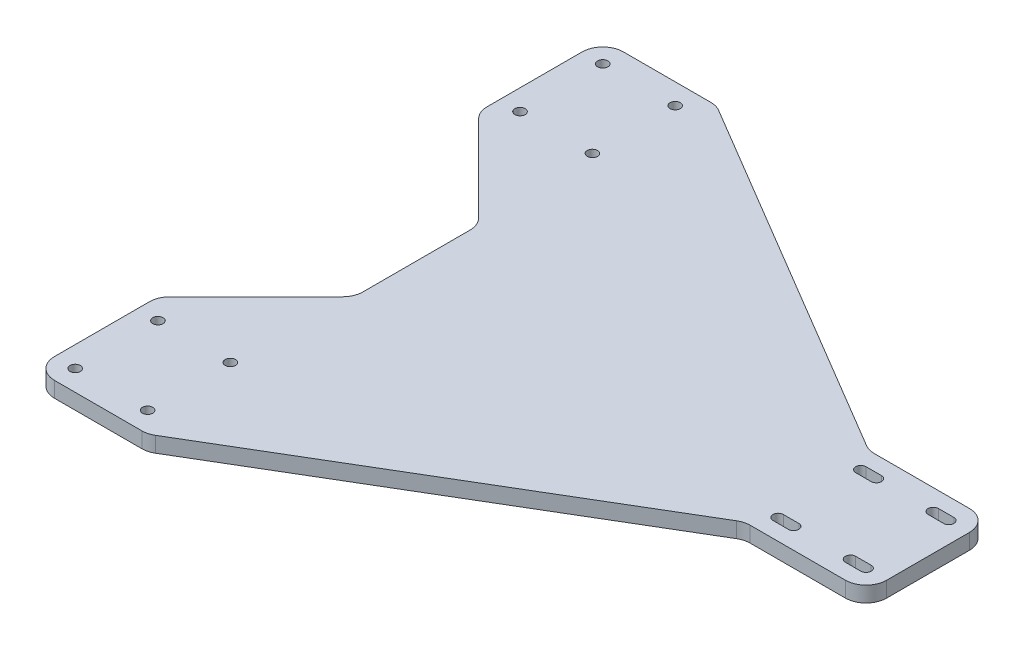
SolidWorks part; units mm, degrees
material "6061-O (SS)"
ref_plane "Plan de face" through (0, 0, 0) normal (0, 0, 1) x (1, 0, 0)
ref_plane "Plan de dessus" through (0, 0, 0) normal (0, 1, 0) x (1, 0, 0)
ref_plane "Plan de droite" through (0, 0, 0) normal (1, 0, 0) x (0, 0, -1)
sketch "Esquisse1" plane through (0, 0, 0) normal (0, 1, 0) x (1, 0, 0)
  line L1 (58.95, -55) -> (-58.95, -55)
  line L2 (58.95, -55) -> (58.95, 55)
  line L3 (58.95, 55) -> (-58.95, 55)
  line L4 (-58.95, -55) -> (-58.95, 55)
  line L5 (58.95, -55) -> (-58.95, 55) construction
  line L6 (58.95, 55) -> (-58.95, -55) construction
  point P0 (0, 0)
  dimension "D1" = 110
  dimension "D2" = 117.9
extrude "Boss.-Extru.1" add sketch "Esquisse1" along normal blind 3
sketch "Esquisse2" plane through (0, 0, 0) normal (0, 1, 0) x (1, 0, 0)
  line L0 (-58.95, -55) -> (58.95, -55) construction
  line L1 (-54.95, -35) -> (-40.95, -35) construction
  line L2 (-54.95, -35) -> (-54.95, -51) construction
  line L3 (-54.95, -51) -> (-40.95, -51) construction
  line L4 (-40.95, -35) -> (-40.95, -51) construction
  line L5 (-54.95, -35) -> (-40.95, -51) construction
  line L6 (-54.95, -51) -> (-40.95, -35) construction
  line L7 (-58.95, 55) -> (-58.95, -55) construction
  line L8 (0, 0) -> (-58.95, 0) construction
  line L9 (-54.95, 51) -> (-40.95, 35) construction
  line L10 (-54.95, 35) -> (-40.95, 51) construction
  line L11 (-40.95, 35) -> (-40.95, 51) construction
  line L12 (-54.95, 51) -> (-40.95, 51) construction
  line L13 (-54.95, 35) -> (-54.95, 51) construction
  line L14 (-54.95, 35) -> (-40.95, 35) construction
  line L15 (46.45, 0) -> (53.45, 8) construction
  line L16 (39.45, 8) -> (53.45, 8) construction
  line L17 (39.45, 8) -> (39.45, -8) construction
  line L18 (39.45, -8) -> (53.45, -8) construction
  line L19 (53.45, 8) -> (53.45, -8) construction
  line L20 (39.45, 8) -> (46.45, 0) construction
  line L21 (39.45, -8) -> (46.45, 0) construction
  line L22 (46.45, 0) -> (53.45, -8) construction
  line L23 (0, 0) -> (58.95, 0) construction
  line L24 (58.95, -55) -> (58.95, 55) construction
  line L25 (58.95, 12) -> (35.45, 12)
  line L26 (35.45, 12) -> (-36.95, 55)
  line L27 (58.95, 55) -> (-58.95, 55) construction
  line L28 (-36.95, 55) -> (58.95, 55)
  line L29 (58.95, 55) -> (58.95, 12)
  line L30 (58.95, -12) -> (35.45, -12)
  line L31 (58.95, -55) -> (58.95, -12)
  line L32 (-36.95, -55) -> (58.95, -55)
  line L33 (35.45, -12) -> (-36.95, -55)
  line L34 (-58.95, -31) -> (-39.95, -12)
  line L35 (-39.95, -12) -> (-39.95, 12)
  line L36 (-39.95, 12) -> (-58.95, 31)
  line L37 (-58.95, 31) -> (-58.95, -31)
  line L38 (37.95, 8) -> (40.95, 8) construction
  line L39 (37.95, 9) -> (40.95, 9)
  line L40 (37.95, 7) -> (40.95, 7)
  line L41 (54.95, 8) -> (51.95, 8) construction
  line L42 (54.95, 7) -> (51.95, 7)
  line L43 (54.95, 9) -> (51.95, 9)
  line L44 (37.95, -8) -> (40.95, -8) construction
  line L45 (37.95, -7) -> (40.95, -7)
  line L46 (37.95, -9) -> (40.95, -9)
  line L47 (54.95, -8) -> (51.95, -8) construction
  line L48 (54.95, -9) -> (51.95, -9)
  line L49 (54.95, -7) -> (51.95, -7)
  circle A0 centre (-40.95, -35) radius 1
  circle A1 centre (-54.95, -35) radius 1
  circle A2 centre (-54.95, -51) radius 1
  circle A3 centre (-40.95, -51) radius 1
  circle A4 centre (-40.95, 51) radius 1
  circle A5 centre (-54.95, 51) radius 1
  circle A6 centre (-54.95, 35) radius 1
  circle A7 centre (-40.95, 35) radius 1
  arc A12 (37.95, 9) -> (37.95, 7) centre (37.95, 8) ccw
  arc A13 (40.95, 7) -> (40.95, 9) centre (40.95, 8) ccw
  arc A14 (54.95, 7) -> (54.95, 9) centre (54.95, 8) ccw
  arc A15 (51.95, 9) -> (51.95, 7) centre (51.95, 8) ccw
  arc A16 (37.95, -7) -> (37.95, -9) centre (37.95, -8) ccw
  arc A17 (40.95, -9) -> (40.95, -7) centre (40.95, -8) ccw
  arc A18 (54.95, -9) -> (54.95, -7) centre (54.95, -8) ccw
  arc A19 (51.95, -7) -> (51.95, -9) centre (51.95, -8) ccw
  point P0 (-47.95, -43)
  point P25 (-47.95, 43)
  point P26 (46.45, 0)
  point P33 (39.45, 8)
  point P52 (-39.95, 0)
  point P58 (53.45, 8)
  point P65 (39.45, -8)
  point P72 (53.45, -8)
  dimension "D3" = 2
  dimension "D4" = 4
  dimension "D5" = 4
  dimension "D6" = 1
  dimension "D1" = 16
  dimension "D2" = 14
  dimension "D7" = 14
  dimension "D8" = 16
  dimension "D9" = 5.5
  dimension "D10" = 4
  dimension "D11" = 4
  dimension "D12" = 4
  dimension "D13" = 4
  dimension "D14" = 4
  dimension "D15" = 4
  dimension "D16" = 1
  dimension "D17" = 1.5
extrude "Enlèv. mat.-Extru.1" cut sketch "Esquisse2" along normal through all
fillet "Congé1" radius 4 12 edges at (35.45, 1.5, 12) (58.95, 1.5, 12) (58.95, 1.5, -12) (35.45, 1.5, -12) (-36.95, 1.5, -55) (-58.95, 1.5, -55) (-58.95, 1.5, -31) (-39.95, 1.5, -12) (-39.95, 1.5, 12) (-58.95, 1.5, 31) (-58.95, 1.5, 55) (-36.95, 1.5, 55)
sketch "Esquisse3" plane through (0, 0, 0) normal (0, 1, 0) x (1, 0, 0)
  line L1 (11, -11) -> (-11, -11) construction
  line L2 (11, -11) -> (11, 11) construction
  line L3 (11, 11) -> (-11, 11) construction
  line L4 (-11, -11) -> (-11, 11) construction
  line L5 (11, -11) -> (-11, 11) construction
  line L6 (11, 11) -> (-11, -11) construction
  line L7 (-11.5, 11) -> (-10.5, 11) construction
  line L8 (-11.5, 13) -> (-10.5, 13)
  line L9 (-11.5, 9) -> (-10.5, 9)
  line L10 (0, 0) -> (-11, 0) construction
  line L11 (0, 0) -> (0, 11) construction
  line L12 (11.5, 11) -> (10.5, 11) construction
  line L13 (11.5, 13) -> (10.5, 13)
  line L14 (11.5, 9) -> (10.5, 9)
  line L15 (11.5, -11) -> (10.5, -11) construction
  line L16 (11.5, -13) -> (10.5, -13)
  line L17 (11.5, -9) -> (10.5, -9)
  line L18 (-11.5, -11) -> (-10.5, -11) construction
  line L19 (-11.5, -13) -> (-10.5, -13)
  line L20 (-11.5, -9) -> (-10.5, -9)
  arc A4 (-11.5, 13) -> (-11.5, 9) centre (-11.5, 11) ccw
  arc A5 (-10.5, 9) -> (-10.5, 13) centre (-10.5, 11) ccw
  arc A6 (11.5, 13) -> (11.5, 9) centre (11.5, 11) cw
  arc A7 (10.5, 9) -> (10.5, 13) centre (10.5, 11) cw
  arc A8 (11.5, -13) -> (11.5, -9) centre (11.5, -11) ccw
  arc A9 (10.5, -9) -> (10.5, -13) centre (10.5, -11) ccw
  arc A10 (-11.5, -13) -> (-11.5, -9) centre (-11.5, -11) cw
  arc A11 (-10.5, -9) -> (-10.5, -13) centre (-10.5, -11) cw
  circle A12 centre (0, 0) radius 8
  point P0 (0, 0)
  point P8 (-11, 11)
  point P22 (11, 11)
  point P29 (11, -11)
  point P36 (-11, -11)
  dimension "D3" = 2
  dimension "D6" = 16
  dimension "D1" = 22
  dimension "D2" = 22
  dimension "D5" = 0.5
extrude "Enlèv. mat.-Extru.2" [suppressed] cut sketch "Esquisse3" along normal through all contours A12
sketch "Esquisse4" plane through (0, 0, 0) normal (0, -1, 0) x (1, 0, 0)
  line L4 (0, 0) -> (6.2905, 0) construction
  line L11 (2.9021, 16.3913) -> (0.8595, 12.9521)
  line L13 (1.261, 11.3761) -> (2.2498, 10.7889)
  line L18 (2.2498, 10.7889) -> (4.8796, 15.2168)
  line L19 (4.8796, 15.2168) -> (2.9021, 16.3913)
  line L21 (3.5647, 13.0028) -> (9.7122, 9.3517) construction
  line L22 (7.939, 13.3671) -> (7.3805, 12.4266) construction
  line L23 (0.2722, 11.9634) -> (2.2498, 10.7889) construction
  line L24 (34.5057, 12.5608) -> (-36.0057, 54.4392) construction
  line L25 (0.2722, 11.9634) -> (0.8595, 12.9521) construction
  line L26 (8.3973, 7.1377) -> (11.0271, 11.5657)
  line L27 (9.386, 6.5505) -> (8.3973, 7.1377)
  line L28 (13.0046, 10.3912) -> (10.962, 6.952)
  line L29 (11.0271, 11.5657) -> (13.0046, 10.3912)
  line L36 (-36.0057, -54.4392) -> (34.5057, -12.5608) construction
  line L37 (-20.806, -41.8884) -> (-19.896, -36.9719)
  line L38 (-19.896, -36.9719) -> (-23.6988, -33.7255)
  line L39 (-23.6988, -33.7255) -> (-28.4116, -35.3956)
  line L40 (-28.4116, -35.3956) -> (-29.3216, -40.3121)
  line L41 (-29.3216, -40.3121) -> (-25.5189, -43.5585)
  line L42 (-25.5189, -43.5585) -> (-20.806, -41.8884)
  line L91 (-39.95, 0) -> (-65.3468, 0) construction
  line L92 (-24.2263, -32.4915) -> (-23.3162, -27.575)
  line L153 (-23.3162, -27.575) -> (-27.119, -24.3286)
  line L154 (-27.119, -24.3286) -> (-31.8318, -25.9987)
  line L155 (-31.8318, -25.9987) -> (-32.7418, -30.9152)
  line L156 (-32.7418, -30.9152) -> (-28.9391, -34.1616)
  line L157 (-28.9391, -34.1616) -> (-24.2263, -32.4915)
  line L158 (-27.6465, -23.0945) -> (-26.7364, -18.178)
  line L159 (-26.7364, -18.178) -> (-30.5392, -14.9317)
  line L160 (-30.5392, -14.9317) -> (-35.252, -16.6018)
  line L161 (-35.252, -16.6018) -> (-36.162, -21.5183)
  line L162 (-36.162, -21.5183) -> (-32.3593, -24.7646)
  line L163 (-32.3593, -24.7646) -> (-27.6465, -23.0945)
  line L164 (-14.3782, -34.2279) -> (-13.4681, -29.3115)
  line L165 (-13.4681, -29.3115) -> (-17.2709, -26.0651)
  line L166 (-17.2709, -26.0651) -> (-21.9837, -27.7352)
  line L167 (-21.9837, -27.7352) -> (-22.8938, -32.6517)
  line L168 (-22.8938, -32.6517) -> (-19.091, -35.898)
  line L169 (-19.091, -35.898) -> (-14.3782, -34.2279)
  line L170 (-17.8041, -24.8152) -> (-16.8941, -19.8987)
  line L171 (-16.8941, -19.8987) -> (-20.6968, -16.6524)
  line L172 (-20.6968, -16.6524) -> (-25.4097, -18.3225)
  line L173 (-25.4097, -18.3225) -> (-26.3197, -23.239)
  line L174 (-26.3197, -23.239) -> (-22.5169, -26.4853)
  line L175 (-22.5169, -26.4853) -> (-17.8041, -24.8152)
  line L176 (-34.0743, -30.755) -> (-33.1643, -25.8385)
  line L177 (-33.1643, -25.8385) -> (-36.967, -22.5921)
  line L178 (-36.967, -22.5921) -> (-41.6799, -24.2622)
  line L179 (-41.6799, -24.2622) -> (-42.5899, -29.1787)
  line L180 (-42.5899, -29.1787) -> (-38.7872, -32.4251)
  line L181 (-38.7872, -32.4251) -> (-34.0743, -30.755)
  line L182 (-11.3762, -17.1548) -> (-10.4662, -12.2383)
  line L183 (-10.4662, -12.2383) -> (-14.269, -8.9919)
  line L184 (-14.269, -8.9919) -> (-18.9818, -10.662)
  line L185 (-18.9818, -10.662) -> (-19.8918, -15.5785)
  line L186 (-19.8918, -15.5785) -> (-16.0891, -18.8249)
  line L187 (-16.0891, -18.8249) -> (-11.3762, -17.1548)
  line L188 (-21.2243, -15.4183) -> (-20.3143, -10.5018)
  line L189 (-20.3143, -10.5018) -> (-24.117, -7.2554)
  line L190 (-24.117, -7.2554) -> (-28.8299, -8.9256)
  line L191 (-28.8299, -8.9256) -> (-29.7399, -13.842)
  line L192 (-29.7399, -13.842) -> (-25.9371, -17.0884)
  line L193 (-25.9371, -17.0884) -> (-21.2243, -15.4183)
  line L194 (-24.6388, -6.0372) -> (-23.7287, -1.1207)
  line L195 (-23.7287, -1.1207) -> (-27.5315, 2.1257)
  line L196 (-27.5315, 2.1257) -> (-32.2443, 0.4556)
  line L197 (-32.2443, 0.4556) -> (-33.1544, -4.4609)
  line L198 (-33.1544, -4.4609) -> (-29.3516, -7.7073)
  line L199 (-29.3516, -7.7073) -> (-24.6388, -6.0372)
  line L200 (-14.7907, -7.7736) -> (-13.8806, -2.8572)
  line L201 (-13.8806, -2.8572) -> (-17.6834, 0.3892)
  line L202 (-17.6834, 0.3892) -> (-22.3962, -1.2809)
  line L203 (-22.3962, -1.2809) -> (-23.3063, -6.1974)
  line L204 (-23.3063, -6.1974) -> (-19.5035, -9.4438)
  line L205 (-19.5035, -9.4438) -> (-14.7907, -7.7736)
  line L206 (-18.2109, 1.6233) -> (-17.3008, 6.5398)
  line L207 (-17.3008, 6.5398) -> (-21.1036, 9.7861)
  line L208 (-21.1036, 9.7861) -> (-25.8164, 8.116)
  line L209 (-25.8164, 8.116) -> (-26.7265, 3.1995)
  line L210 (-26.7265, 3.1995) -> (-22.9237, -0.0468)
  line L211 (-22.9237, -0.0468) -> (-18.2109, 1.6233)
  line L212 (-21.6311, 11.0202) -> (-20.7211, 15.9367)
  line L213 (-20.7211, 15.9367) -> (-24.5238, 19.1831)
  line L214 (-24.5238, 19.1831) -> (-29.2366, 17.513)
  line L215 (-29.2366, 17.513) -> (-30.1467, 12.5965)
  line L216 (-30.1467, 12.5965) -> (-26.3439, 9.3501)
  line L217 (-26.3439, 9.3501) -> (-21.6311, 11.0202)
  line L218 (-25.0513, 20.4171) -> (-24.1413, 25.3336)
  line L219 (-24.1413, 25.3336) -> (-27.944, 28.58)
  line L220 (-27.944, 28.58) -> (-32.6568, 26.9099)
  line L221 (-32.6568, 26.9099) -> (-33.5669, 21.9934)
  line L222 (-33.5669, 21.9934) -> (-29.7641, 18.747)
  line L223 (-29.7641, 18.747) -> (-25.0513, 20.4171)
  line L224 (-28.4715, 29.8141) -> (-27.5615, 34.7305)
  line L225 (-27.5615, 34.7305) -> (-31.3642, 37.9769)
  line L226 (-31.3642, 37.9769) -> (-36.0771, 36.3068)
  line L227 (-36.0771, 36.3068) -> (-36.9871, 31.3903)
  line L228 (-36.9871, 31.3903) -> (-33.1843, 28.144)
  line L229 (-33.1843, 28.144) -> (-28.4715, 29.8141)
  line L230 (-28.059, 3.3598) -> (-27.1489, 8.2763)
  line L231 (-27.1489, 8.2763) -> (-30.9517, 11.5226)
  line L232 (-30.9517, 11.5226) -> (-35.6645, 9.8525)
  line L233 (-35.6645, 9.8525) -> (-36.5746, 4.936)
  line L234 (-36.5746, 4.936) -> (-32.7718, 1.6897)
  line L235 (-32.7718, 1.6897) -> (-28.059, 3.3598)
  line L236 (-15.2032, 18.6807) -> (-14.2932, 23.5971)
  line L237 (-14.2932, 23.5971) -> (-18.0959, 26.8435)
  line L238 (-18.0959, 26.8435) -> (-22.8088, 25.1734)
  line L239 (-22.8088, 25.1734) -> (-23.7188, 20.2569)
  line L240 (-23.7188, 20.2569) -> (-19.9161, 17.0105)
  line L241 (-19.9161, 17.0105) -> (-15.2032, 18.6807)
  line L242 (-8.7754, 26.3411) -> (-7.8653, 31.2576)
  line L243 (-7.8653, 31.2576) -> (-11.6681, 34.504)
  line L244 (-11.6681, 34.504) -> (-16.3809, 32.8338)
  line L245 (-16.3809, 32.8338) -> (-17.2909, 27.9174)
  line L246 (-17.2909, 27.9174) -> (-13.4882, 24.671)
  line L247 (-13.4882, 24.671) -> (-8.7754, 26.3411)
  line L248 (-18.6234, 28.0776) -> (-17.7134, 32.9941)
  line L249 (-17.7134, 32.9941) -> (-21.5161, 36.2404)
  line L250 (-21.5161, 36.2404) -> (-26.229, 34.5703)
  line L251 (-26.229, 34.5703) -> (-27.139, 29.6538)
  line L252 (-27.139, 29.6538) -> (-23.3363, 26.4075)
  line L253 (-23.3363, 26.4075) -> (-18.6234, 28.0776)
  line L254 (-22.0436, 37.4745) -> (-21.1336, 42.391)
  line L255 (-21.1336, 42.391) -> (-24.9363, 45.6374)
  line L256 (-24.9363, 45.6374) -> (-29.6492, 43.9672)
  line L257 (-29.6492, 43.9672) -> (-30.5592, 39.0508)
  line L258 (-30.5592, 39.0508) -> (-26.7565, 35.8044)
  line L259 (-26.7565, 35.8044) -> (-22.0436, 37.4745)
  line L260 (-34.8994, 22.1536) -> (-33.9893, 27.0701)
  line L261 (-33.9893, 27.0701) -> (-37.7921, 30.3165)
  line L262 (-37.7921, 30.3165) -> (-42.5049, 28.6464)
  line L263 (-42.5049, 28.6464) -> (-43.415, 23.7299)
  line L264 (-43.415, 23.7299) -> (-39.6122, 20.4835)
  line L265 (-39.6122, 20.4835) -> (-34.8994, 22.1536)
  line L266 (-31.4792, 12.7567) -> (-30.5691, 17.6732)
  line L267 (-30.5691, 17.6732) -> (-34.3719, 20.9195)
  line L268 (-34.3719, 20.9195) -> (-39.0847, 19.2494)
  line L269 (-39.0847, 19.2494) -> (-39.9948, 14.333)
  line L270 (-39.9948, 14.333) -> (-36.192, 11.0866)
  line L271 (-36.192, 11.0866) -> (-31.4792, 12.7567)
  line L272 (-11.783, 9.2837) -> (-10.873, 14.2002)
  line L273 (-10.873, 14.2002) -> (-14.6757, 17.4466)
  line L274 (-14.6757, 17.4466) -> (-19.3886, 15.7765)
  line L275 (-19.3886, 15.7765) -> (-20.2986, 10.86)
  line L276 (-20.2986, 10.86) -> (-16.4959, 7.6136)
  line L277 (-16.4959, 7.6136) -> (-11.783, 9.2837)
  line L278 (-7.956, -26.5517) -> (-7.046, -21.6352)
  line L279 (-7.046, -21.6352) -> (-10.8488, -18.3889)
  line L280 (-10.8488, -18.3889) -> (-15.5616, -20.059)
  line L281 (-15.5616, -20.059) -> (-16.4716, -24.9755)
  line L282 (-16.4716, -24.9755) -> (-12.6689, -28.2218)
  line L283 (-12.6689, -28.2218) -> (-7.956, -26.5517)
  line L284 (-1.5282, -18.8913) -> (-0.6181, -13.9748)
  line L285 (-0.6181, -13.9748) -> (-4.4209, -10.7284)
  line L286 (-4.4209, -10.7284) -> (-9.1337, -12.3985)
  line L287 (-9.1337, -12.3985) -> (-10.0438, -17.315)
  line L288 (-10.0438, -17.315) -> (-6.241, -20.5614)
  line L289 (-6.241, -20.5614) -> (-1.5282, -18.8913)
  line L290 (8.3199, -20.6277) -> (9.23, -15.7113)
  line L291 (9.23, -15.7113) -> (5.4272, -12.4649)
  line L292 (5.4272, -12.4649) -> (0.7144, -14.135)
  line L293 (0.7144, -14.135) -> (-0.1957, -19.0515)
  line L294 (-0.1957, -19.0515) -> (3.6071, -22.2979)
  line L295 (3.6071, -22.2979) -> (8.3199, -20.6277)
  line L296 (14.7478, -12.9673) -> (15.6578, -8.0508)
  line L297 (15.6578, -8.0508) -> (11.8551, -4.8044)
  line L298 (11.8551, -4.8044) -> (7.1422, -6.4746)
  line L299 (7.1422, -6.4746) -> (6.2322, -11.391)
  line L300 (6.2322, -11.391) -> (10.035, -14.6374)
  line L301 (10.035, -14.6374) -> (14.7478, -12.9673)
  line L302 (21.1757, -5.3069) -> (22.0857, -0.3904)
  line L303 (22.0857, -0.3904) -> (18.2829, 2.856)
  line L304 (18.2829, 2.856) -> (13.5701, 1.1859)
  line L305 (13.5701, 1.1859) -> (12.6601, -3.7306)
  line L306 (12.6601, -3.7306) -> (16.4628, -6.977)
  line L307 (16.4628, -6.977) -> (21.1757, -5.3069)
  line L308 (27.6035, 2.3536) -> (28.5136, 7.2701)
  line L309 (28.5136, 7.2701) -> (24.7108, 10.5164)
  line L310 (24.7108, 10.5164) -> (19.998, 8.8463)
  line L311 (19.998, 8.8463) -> (19.0879, 3.9298)
  line L312 (19.0879, 3.9298) -> (22.8907, 0.6835)
  line L313 (22.8907, 0.6835) -> (27.6035, 2.3536)
  line L314 (24.5959, -14.7038) -> (25.5059, -9.7873)
  line L315 (25.5059, -9.7873) -> (21.7031, -6.5409)
  line L316 (21.7031, -6.5409) -> (16.9903, -8.211)
  line L317 (16.9903, -8.211) -> (16.0803, -13.1275)
  line L318 (16.0803, -13.1275) -> (19.883, -16.3739)
  line L319 (19.883, -16.3739) -> (24.5959, -14.7038)
  line L320 (31.0237, -7.0433) -> (31.9338, -2.1269)
  line L321 (31.9338, -2.1269) -> (28.131, 1.1195)
  line L322 (28.131, 1.1195) -> (23.4182, -0.5506)
  line L323 (23.4182, -0.5506) -> (22.5081, -5.4671)
  line L324 (22.5081, -5.4671) -> (26.3109, -8.7135)
  line L325 (26.3109, -8.7135) -> (31.0237, -7.0433)
  line L326 (37.4516, 0.6171) -> (38.3617, 5.5336)
  line L327 (38.3617, 5.5336) -> (34.5589, 8.78)
  line L328 (34.5589, 8.78) -> (29.8461, 7.1098)
  line L329 (29.8461, 7.1098) -> (28.936, 2.1934)
  line L330 (28.936, 2.1934) -> (32.7388, -1.053)
  line L331 (32.7388, -1.053) -> (37.4516, 0.6171)
  line L332 (-5.3551, 16.9442) -> (-4.4451, 21.8607)
  line L333 (-4.4451, 21.8607) -> (-8.2479, 25.107)
  line L334 (-8.2479, 25.107) -> (-12.9607, 23.4369)
  line L335 (-12.9607, 23.4369) -> (-13.8707, 18.5204)
  line L336 (-13.8707, 18.5204) -> (-10.068, 15.2741)
  line L337 (-10.068, 15.2741) -> (-5.3551, 16.9442)
  line L338 (1.892, -28.2882) -> (2.8021, -23.3717)
  line L339 (2.8021, -23.3717) -> (-1.0007, -20.1253)
  line L340 (-1.0007, -20.1253) -> (-5.7135, -21.7954)
  line L341 (-5.7135, -21.7954) -> (-6.6236, -26.7119)
  line L342 (-6.6236, -26.7119) -> (-2.8208, -29.9583)
  line L343 (-2.8208, -29.9583) -> (1.892, -28.2882)
  arc A14 (1.261, 11.3761) -> (0.8595, 12.9521) centre (1.8483, 12.3649) cw
  arc A15 (9.386, 6.5505) -> (10.962, 6.952) centre (9.9733, 7.5393) ccw
  circle A16 centre (-24.6088, -38.642) radius 4.3301 construction
  point P8 (6.6384, 11.1773)
  point P37 (0.2722, 11.9634)
  dimension "D1" = 7.15
  dimension "D2" = 5.15
  dimension "D3" = 2.3
  dimension "D5" = 1.15
  dimension "D12" = 2
  dimension "D13" = 2
  dimension "D4" = 13
  dimension "D6" = 5
  dimension "D7" = 3
  dimension "D8" = 2
  dimension "D9" = 2
  dimension "D10" = 2
  dimension "D11" = 2
  dimension "D21" = 4
  dimension "D25" = 11.194
  dimension "D26" = 3
  dimension "D14" = 2
  dimension "D16" = 2
  dimension "D15" = 2
  dimension "D18" = 5
  dimension "D17" = 2
  dimension "D19" = 3
  dimension "D20" = 2
  dimension "D22" = 2
  dimension "D23" = 3
  dimension "D24" = 2
extrude "Enlèv. mat.-Extru.3" [suppressed] cut sketch "Esquisse4" against normal through all
